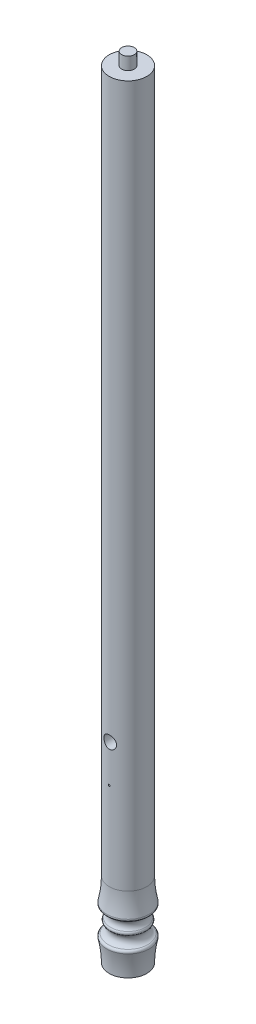
SolidWorks part; units mm, degrees
ref_plane "Front Plane" through (0, 0, 0) normal (0, 0, 1) x (1, 0, 0)
ref_plane "Top Plane" through (0, 0, 0) normal (0, 1, 0) x (1, 0, 0)
ref_plane "Right Plane" through (0, 0, 0) normal (1, 0, 0) x (0, 0, -1)
ref_plane "Plane3" through (0, 787.4, 0) normal (0, 1, 0) x (1, 0, 0)
ref_plane "Plane4" through (0, 800.1, 0) normal (0, 1, 0) x (1, 0, 0)
ref_plane "Plane5" through (0, 165.1, 0) normal (0, 1, 0) x (1, 0, 0)
ref_plane "Plane6" through (0, 203.2, 0) normal (0, 1, 0) x (1, 0, 0)
ref_plane "Plane7" through (0, 254, 0) normal (0, 1, 0) x (1, 0, 0)
ref_plane "Plane8" through (0, 25.4, 0) normal (0, 1, 0) x (1, 0, 0)
ref_plane "Plane9" through (0, 38.1, 0) normal (0, 1, 0) x (1, 0, 0)
ref_plane "Plane10" through (0, 50.8, 0) normal (0, 1, 0) x (1, 0, 0)
ref_plane "Plane11" through (0, 76.2, 0) normal (0, 1, 0) x (1, 0, 0)
ref_plane "Plane14" through (6.35, 0, 0) normal (1, 0, 0) x (0, 0, -1)
ref_plane "Plane15" through (15.875, 0, 0) normal (1, 0, 0) x (0, 0, -1)
ref_plane "Plane16" through (19.05, 0, 0) normal (1, 0, 0) x (0, 0, -1)
ref_plane "Plane17" through (22.225, 0, 0) normal (1, 0, 0) x (0, 0, -1)
sketch "center" plane through (0, 0, 0) normal (0, 0, 1) x (1, 0, 0)
  line L0 (0, 0) -> (0, 787.4)
  line L7 (154.1749, 787.4) -> (-154.1749, 787.4) construction
  line L13 (0, -76.5499) -> (0, 76.5499) construction
ref_axis "Axis1" through (0, -55, 0) along (0, 1, 0)
sketch "Sketch5" plane through (0, 25.4, 0) normal (0, 1, 0) x (1, 0, 0)
  line L0 (22.225, -76.5499) -> (22.225, 76.5499) construction
  circle A0 centre (0, 0) radius 22.225
ref_plane "Plane18" through (0, 31.75, 0) normal (0, 1, 0) x (1, 0, 0)
ref_plane "Plane19" through (0, 44.45, 0) normal (0, 1, 0) x (1, 0, 0)
sketch "Sketch6" plane through (0, 31.75, 0) normal (0, 1, 0) x (1, 0, 0)
  line L0 (15.875, -76.5499) -> (15.875, 76.5499) construction
  circle A0 centre (0, 0) radius 15.875
sketch "Sketch7" plane through (0, 38.1, 0) normal (0, 1, 0) x (1, 0, 0)
  circle A0 centre (0, 0) radius 18.9864
sketch "Sketch8" plane through (0, 44.45, 0) normal (0, 1, 0) x (1, 0, 0)
  circle A0 centre (0, 0) radius 15.875
sketch "Sketch9" plane through (0, 50.8, 0) normal (0, 1, 0) x (1, 0, 0)
  circle A0 centre (0, 0) radius 22.225
sketch "Sketch10" plane through (0, 76.2, 0) normal (0, 1, 0) x (1, 0, 0)
  circle A0 centre (0, 0) radius 18.9864
sketch "Sketch11" plane through (0, 0, 0) normal (0, 1, 0) x (1, 0, 0)
  circle A0 centre (0, 0) radius 18.9864
sketch "revolve sketch" plane through (0, 0, 0) normal (0, 0, 1) x (1, 0, 0)
  line L0 (0, 0) -> (19.05, 0)
  line L1 (18.9864, 0) -> (-18.9864, 0) construction
  line L2 (15.875, -76.5499) -> (15.875, 76.5499) construction
  line L3 (22.225, 25.4) -> (-22.225, 25.4) construction
  line L4 (22.225, -76.5499) -> (22.225, 76.5499) construction
  line L5 (154.1749, 25.4) -> (-154.1749, 25.4) construction
  line L6 (15.875, 31.75) -> (-15.875, 31.75) construction
  line L7 (154.1749, 31.75) -> (-154.1749, 31.75) construction
  line L8 (154.1749, 38.1) -> (-154.1749, 38.1) construction
  line L9 (15.875, 44.45) -> (-15.875, 44.45) construction
  line L10 (154.1749, 44.45) -> (-154.1749, 44.45) construction
  line L11 (22.225, 50.8) -> (-22.225, 50.8) construction
  line L12 (154.1749, 50.8) -> (-154.1749, 50.8) construction
  line L17 (19.05, -76.5499) -> (19.05, 76.5499) construction
  line L18 (154.1749, 0) -> (-154.1749, 0) construction
  line L19 (18.9864, 76.2) -> (-18.9864, 76.2) construction
  line L20 (154.1749, 76.2) -> (-154.1749, 76.2) construction
  line L21 (19.05, 76.2) -> (19.05, 787.4)
  line L22 (154.1749, 787.4) -> (-154.1749, 787.4) construction
  line L23 (19.05, 787.4) -> (6.35, 787.4)
  line L24 (6.35, -76.5499) -> (6.35, 76.5499) construction
  line L25 (6.35, 787.4) -> (6.35, 800.1)
  line L26 (152.7724, 800.1) -> (-152.7724, 800.1) construction
  line L27 (6.35, 800.1) -> (0, 800.1)
  line L28 (0, -76.5499) -> (0, 76.5499) construction
  line L29 (0, 800.1) -> (0, 0)
  arc A0 (19.05, 0) -> (21.6122, 22.8517) centre (122.2375, 0) cw
  arc A1 (15.875, 31.75) -> (20.018, 25.7959) centre (22.225, 31.75) ccw
  arc A2 (15.875, 31.75) -> (17.7809, 36.2857) centre (22.225, 31.75) cw
  arc A3 (17.7809, 39.9143) -> (15.875, 44.45) centre (22.225, 44.45) cw
  arc A4 (15.875, 44.45) -> (20.018, 50.4041) centre (22.225, 44.45) cw
  arc A5 (21.6122, 53.3483) -> (19.05, 76.2) centre (122.2375, 76.2) cw
  arc A6 (17.7809, 36.2857) -> (17.7809, 39.9143) centre (16.0033, 38.1) ccw
  arc A7 (21.6122, 22.8517) -> (20.018, 25.7959) centre (19.1352, 23.4142) ccw
  arc A8 (20.018, 50.4041) -> (21.6122, 53.3483) centre (19.1352, 52.7858) ccw
  point P49 (22.225, 38.1)
  point P52 (22.225, 25.4)
  point P55 (22.225, 50.8)
  point P60 (22.225, 25.4)
  point P62 (22.225, 50.8)
  dimension "D1" = 2.54
  dimension "D2" = 2.54
  dimension "D3" = 2.54
revolve "Revolve1" add sketch "revolve sketch" angle 360 about axis through (0, -55, 0) along (0, 1, 0)
ref_plane "Plane20" through (0, 317.5, 0) normal (0, 1, 0) x (1, 0, 0)
ref_axis "Axis2" through (162.1372, 317.5, 0) along (-1, 0, 0)
ref_axis "Axis3" through (0, 254, -88.99) along (0, 0, 1)
ref_axis "Axis4" through (0, 203.2, -88.99) along (0, 0, 1)
ref_axis "Axis5" through (0, 165.1, -88.99) along (0, 0, 1)
ref_plane "Plane21" through (0, 0, 6.35) normal (0, 0, 1) x (1, 0, 0)
ref_plane "Plane22" through (0, 0, 19.05) normal (0, 0, 1) x (1, 0, 0)
sketch "Sketch15" plane through (0, 0, 19.05) normal (0, 0, 1) x (1, 0, 0)
  line L0 (0, 0) -> (0, 787.4) construction
  line L1 (142.5044, 254) -> (-142.5044, 254) construction
  circle A0 centre (0, 254) radius 0.9922
  dimension "D1" = 1.9844
sketch "Sketch16" plane through (19.05, 0, 0) normal (1, 0, 0) x (0, 0, -1)
  line L0 (142.5044, 317.5) -> (-142.5044, 317.5) construction
  line L1 (0, 0) -> (0, 787.4) construction
  circle A0 centre (0, 317.5) radius 0.9922
  dimension "D1" = 1.9844
sketch "Sketch17" plane through (0, 0, 19.05) normal (0, 0, 1) x (1, 0, 0)
  line L0 (0, 0) -> (0, 787.4) construction
  line L1 (174.8529, 203.2) -> (-174.8529, 203.2) construction
  circle A0 centre (0, 203.2) radius 6.35
  dimension "D1" = 12.7
extrude "Cut-Extrude3" cut sketch "Sketch17" against normal up to surface (19.05 mm away) contours A0 up to plane "Front Plane"
sketch "Sketch18" plane through (0, 0, 19.05) normal (0, 0, 1) x (1, 0, 0)
  line L0 (172.3771, 165.1) -> (-172.3771, 165.1) construction
  circle A0 centre (0, 165.1) radius 0.9922
  dimension "D1" = 1.9844
extrude "Cut-Extrude4" cut sketch "Sketch18" against normal up to surface (12.7 mm away) up to plane "Plane21"
ref_plane "Plane23" through (-19.05, 0, 0) normal (-1, 0, 0) x (0, 0, 1)
ref_plane "Plane24" through (-6.35, 0, 0) normal (-1, 0, 0) x (0, 0, 1)
sketch "Sketch19" plane through (-19.05, 0, 0) normal (-1, 0, 0) x (0, 0, 1)
  line L0 (0, 0) -> (0, 787.4) construction
  line L1 (142.5044, 317.5) -> (-142.5044, 317.5) construction
  circle A0 centre (0, 317.5) radius 0.9922
extrude "Cut-Extrude5" cut sketch "Sketch19" against normal up to surface (12.7 mm away) up to plane "Plane24"
ref_plane "Plane25" through (0, 0, -19.05) normal (0, 0, 1) x (1, 0, 0)
